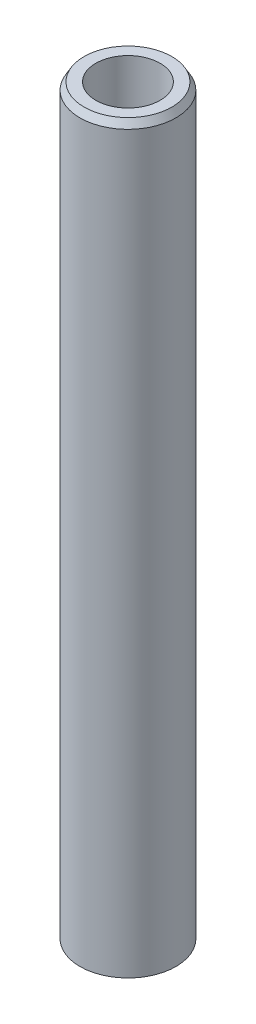
SolidWorks part; units mm, degrees
ref_plane "Front Plane" through (0, 0, 0) normal (0, 0, 1) x (1, 0, 0)
ref_plane "Top Plane" through (0, 0, 0) normal (0, 1, 0) x (1, 0, 0)
ref_plane "Right Plane" through (0, 0, 0) normal (1, 0, 0) x (0, 0, -1)
sketch "Sketch1" plane through (0, 0, 0) normal (0, 1, 0) x (1, 0, 0)
  circle A0 centre (0, 0) radius 10
  dimension "SHAFT_OD" = 20
extrude "Boss-Extrude1" add sketch "Sketch1" along normal blind 155.4245
sketch "Sketch2" plane through (0, 0, 0) normal (0, 1, 0) x (1, 0, 0)
  circle A0 centre (0, 0) radius 6.6964
  dimension "BORE_D" = 13.3928
extrude "Cut-Extrude1" cut sketch "Sketch2" along normal through all
chamfer "Chamfer1" distance 1.504 angle 30 2 edges at (0, 155.4245, 10) (0, 0, 10) first distance on face at (0, 155.4245, 10) first distance on face at (0, 0, 6.6964)
